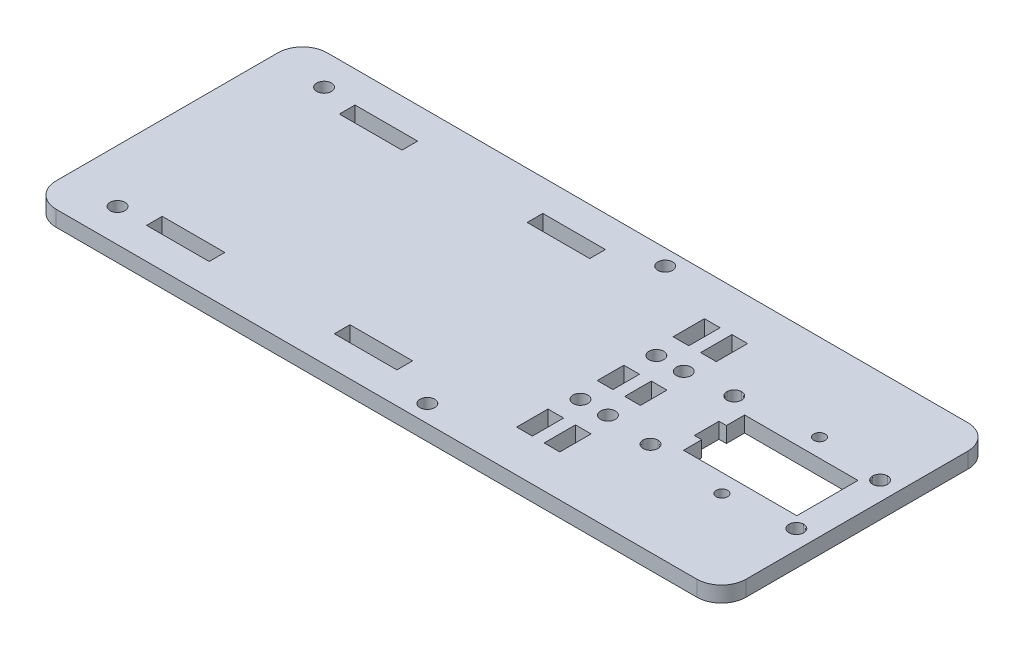
SolidWorks part; units mm, degrees
ref_plane "Front Plane" through (0, 0, 0) normal (0, 0, 1) x (1, 0, 0)
ref_plane "Top Plane" through (0, 0, 0) normal (0, 1, 0) x (1, 0, 0)
ref_plane "Right Plane" through (0, 0, 0) normal (1, 0, 0) x (0, 0, -1)
sketch "Sketch1" plane through (0, 0, 0) normal (0, 1, 0) x (1, 0, 0)
  line L0 (93.175, 40.2) -> (93.175, 14.8) construction
  line L1 (5, 0) -> (135, 0)
  line L2 (0, 5) -> (0, 50)
  line L3 (5, 55) -> (135, 55)
  line L4 (140, 5) -> (140, 50)
  line L5 (140, 27.5) -> (116.4302, 27.5) construction
  line L6 (90, 46.55) -> (93.175, 46.55)
  line L7 (90, 46.55) -> (90, 40.2)
  line L8 (90, 40.2) -> (93.175, 40.2)
  line L9 (93.175, 46.55) -> (93.175, 40.2)
  line L10 (90, 14.8) -> (93.175, 14.8)
  line L11 (90, 14.8) -> (90, 8.45)
  line L12 (90, 8.45) -> (93.175, 8.45)
  line L13 (93.175, 14.8) -> (93.175, 8.45)
  line L14 (93.175, 27.5) -> (47.2685, 27.5) construction
  line L15 (0, 27.5) -> (7.7524, 27.5) construction
  line L16 (91.5875, 40.2) -> (91.5875, 30.2) construction
  line L17 (93.175, 30.2) -> (90, 30.2)
  line L18 (93.175, 30.2) -> (93.175, 24.8)
  line L19 (93.175, 24.8) -> (90, 24.8)
  line L20 (90, 30.2) -> (90, 24.8)
  line L21 (91.5875, 24.8) -> (91.5875, 14.8) construction
  line L22 (95.575, 46.55) -> (98.75, 46.55)
  line L23 (95.575, 46.55) -> (95.575, 40.2)
  line L24 (95.575, 40.2) -> (98.75, 40.2)
  line L25 (98.75, 46.55) -> (98.75, 40.2)
  line L26 (95.575, 30.2) -> (98.75, 30.2)
  line L27 (95.575, 30.2) -> (95.575, 24.8)
  line L28 (95.575, 24.8) -> (98.75, 24.8)
  line L29 (98.75, 30.2) -> (98.75, 24.8)
  line L30 (95.575, 14.8) -> (98.75, 14.8)
  line L31 (95.575, 14.8) -> (95.575, 8.45)
  line L32 (95.575, 8.45) -> (98.75, 8.45)
  line L33 (98.75, 14.8) -> (98.75, 8.45)
  line L34 (97.1625, 40.2) -> (97.1625, 30.2) construction
  line L35 (97.1625, 24.8) -> (97.1625, 14.8) construction
  line L36 (90, 27.5) -> (93.175, 27.5) construction
  line L37 (98.75, 27.5) -> (95.575, 27.5) construction
  line L38 (67.8, 6.35) -> (67.8, 9.525)
  line L39 (17, 48.65) -> (29.7, 48.65)
  line L40 (17, 48.65) -> (17, 45.475)
  line L41 (17, 45.475) -> (29.7, 45.475)
  line L42 (29.7, 48.65) -> (29.7, 45.475)
  line L43 (55.1, 48.65) -> (67.8, 48.65)
  line L44 (55.1, 48.65) -> (55.1, 45.475)
  line L45 (55.1, 45.475) -> (67.8, 45.475)
  line L46 (67.8, 48.65) -> (67.8, 45.475)
  line L47 (55.1, 9.525) -> (67.8, 9.525)
  line L48 (55.1, 6.35) -> (55.1, 9.525)
  line L49 (55.1, 6.35) -> (67.8, 6.35)
  line L50 (29.7, 6.35) -> (29.7, 9.525)
  line L51 (17, 9.525) -> (29.7, 9.525)
  line L52 (17, 6.35) -> (17, 9.525)
  line L53 (17, 6.35) -> (29.7, 6.35)
  line L54 (116.5, 33.7) -> (128.5, 33.7)
  line L55 (116.5, 21.3) -> (131.3, 21.3)
  line L56 (134, 27.5) -> (109.5001, 27.5) construction
  line L57 (109.5001, 25) -> (111, 25)
  line L58 (111, 25) -> (111, 21.3)
  line L59 (111, 21.3) -> (116.5, 21.3)
  line L63 (131.3, 21.3) -> (134, 21.3)
  line L64 (134, 21.3) -> (134, 33.7)
  line L65 (134, 33.7) -> (128.5, 33.7)
  line L69 (116.5, 33.7) -> (111, 33.7)
  line L70 (111, 33.7) -> (111, 30)
  line L71 (111, 30) -> (109.5001, 30)
  line L72 (109.5001, 30) -> (109.5001, 25)
  circle A0 centre (91.5875, 35.2) radius 1.5
  circle A1 centre (97.1625, 35.2) radius 1.5
  circle A2 centre (91.5875, 19.8) radius 1.5
  circle A3 centre (97.1625, 19.8) radius 1.5
  circle A4 centre (10.7398, 48.6273) radius 1.5
  circle A5 centre (10.7398, 6.7173) radius 1.5
  circle A6 centre (76.7798, 3.5423) radius 1.5
  circle A7 centre (76.7798, 51.8023) radius 1.5
  arc A8 (135, 55) -> (140, 50) centre (135, 50) cw
  arc A9 (135, 0) -> (140, 5) centre (135, 5) ccw
  arc A10 (5, 0) -> (0, 5) centre (5, 5) cw
  arc A11 (0, 50) -> (5, 55) centre (5, 50) cw
  circle A12 centre (122.5, 37.4) radius 1.15
  circle A13 centre (122.5, 17.6) radius 1.15
  spline S0 degree 3 poles (108.1, 36) (108.1, 35.1715) (107.4285, 34.5) (106.6001, 34.5) knots 0 0 0 0 0.2 0.2 0.2 0.2
  spline S1 degree 3 poles (106.6001, 34.5) (105.7716, 34.4999) (105.1001, 35.1715) (105.1001, 35.9999) knots 0.2 0.2 0.2 0.2 0.4 0.4 0.4 0.4
  spline S2 degree 3 poles (105.1001, 35.9999) (105.1, 36.8284) (105.7716, 37.4999) (106.6, 37.5) knots 0.4 0.4 0.4 0.4 0.6 0.6 0.6 0.6
  spline S3 degree 3 poles (106.6, 37.5) (107.4285, 37.5) (108.1, 36.8284) (108.1, 36) knots 0.6 0.6 0.6 0.6 1 1 1 1
  spline S4 degree 3 poles (137.7, 19.0002) (137.7, 18.1718) (137.0284, 17.5002) (136.2001, 17.5002) knots 0 0 0 0 0.2 0.2 0.2 0.2
  spline S5 degree 3 poles (136.2001, 17.5002) (135.3717, 17.5002) (134.7001, 18.1718) (134.7001, 19.0001) knots 0.2 0.2 0.2 0.2 0.4 0.4 0.4 0.4
  spline S6 degree 3 poles (134.7001, 19.0001) (134.7001, 19.8285) (135.3717, 20.4999) (136.2, 20.4999) knots 0.4 0.4 0.4 0.4 0.6 0.6 0.6 0.6
  spline S7 degree 3 poles (136.2, 20.4999) (137.0284, 20.4999) (137.7, 19.8285) (137.7, 19.0002) knots 0.6 0.6 0.6 0.6 1 1 1 1
  spline S8 degree 3 poles (108.1, 19.0002) (108.1, 18.1718) (107.4284, 17.5001) (106.6001, 17.5001) knots 0 0 0 0 0.2 0.2 0.2 0.2
  spline S9 degree 3 poles (106.6001, 17.5001) (105.7717, 17.5001) (105.1, 18.1718) (105.1, 19.0001) knots 0.2 0.2 0.2 0.2 0.4 0.4 0.4 0.4
  spline S10 degree 3 poles (105.1, 19.0001) (105.1, 19.8285) (105.7717, 20.5) (106.6, 20.5) knots 0.4 0.4 0.4 0.4 0.6 0.6 0.6 0.6
  spline S11 degree 3 poles (106.6, 20.5) (107.4284, 20.5) (108.1, 19.8285) (108.1, 19.0002) knots 0.6 0.6 0.6 0.6 1 1 1 1
  spline S12 degree 3 poles (137.7, 36) (137.7, 35.1715) (137.0285, 34.5001) (136.2001, 34.5001) knots 0 0 0 0 0.2 0.2 0.2 0.2
  spline S13 degree 3 poles (136.2001, 34.5001) (135.3716, 34.5) (134.7002, 35.1715) (134.7002, 35.9999) knots 0.2 0.2 0.2 0.2 0.4 0.4 0.4 0.4
  spline S14 degree 3 poles (134.7002, 35.9999) (134.7001, 36.8284) (135.3716, 37.4998) (136.2, 37.4999) knots 0.4 0.4 0.4 0.4 0.6 0.6 0.6 0.6
  spline S15 degree 3 poles (136.2, 37.4999) (137.0285, 37.4999) (137.7, 36.8284) (137.7, 36) knots 0.6 0.6 0.6 0.6 1 1 1 1
  point P70 (10.7398, 48.6273)
  point P71 (10.7398, 6.7173)
  point P72 (76.7798, 51.8023)
  point P73 (76.7798, 3.5423)
  point P85 (140, 55)
  point P90 (0, 0)
  point P93 (0, 55)
  dimension "D19" = 3
  dimension "D20" = 3
  dimension "D21" = 3
  dimension "D22" = 3
  dimension "D34" = 3
  dimension "D35" = 3
  dimension "D36" = 3
  dimension "D37" = 3
  dimension "D38" = 5
  dimension "D39" = 2.3
  dimension "D1" = 140
  dimension "D2" = 0
  dimension "D3" = 55
  dimension "D4" = 3.175
  dimension "D5" = 3.175
  dimension "D6" = 6.35
  dimension "D7" = 6.35
  dimension "D8" = 38.1
  dimension "D9" = 0
  dimension "D10" = 90
  dimension "D11" = 5.4
  dimension "D12" = 5.4
  dimension "D13" = 2.4
  dimension "D14" = 2.4
  dimension "D15" = 2.4
  dimension "D16" = 3.175
  dimension "D17" = 3.175
  dimension "D18" = 3.175
  dimension "D23" = 0
  dimension "D24" = 0
  dimension "D25" = 12.7
  dimension "D26" = 12.7
  dimension "D27" = 25.4
  dimension "D28" = 17
  dimension "D29" = 6.35
  dimension "D30" = 6.35
  dimension "D31" = 3.175
  dimension "D32" = 3.175
  dimension "D33" = 6
  dimension "D40" = 9.9
  dimension "D41" = 11.5
extrude "Boss-Extrude1" add sketch "Sketch1" along normal blind 3.175
